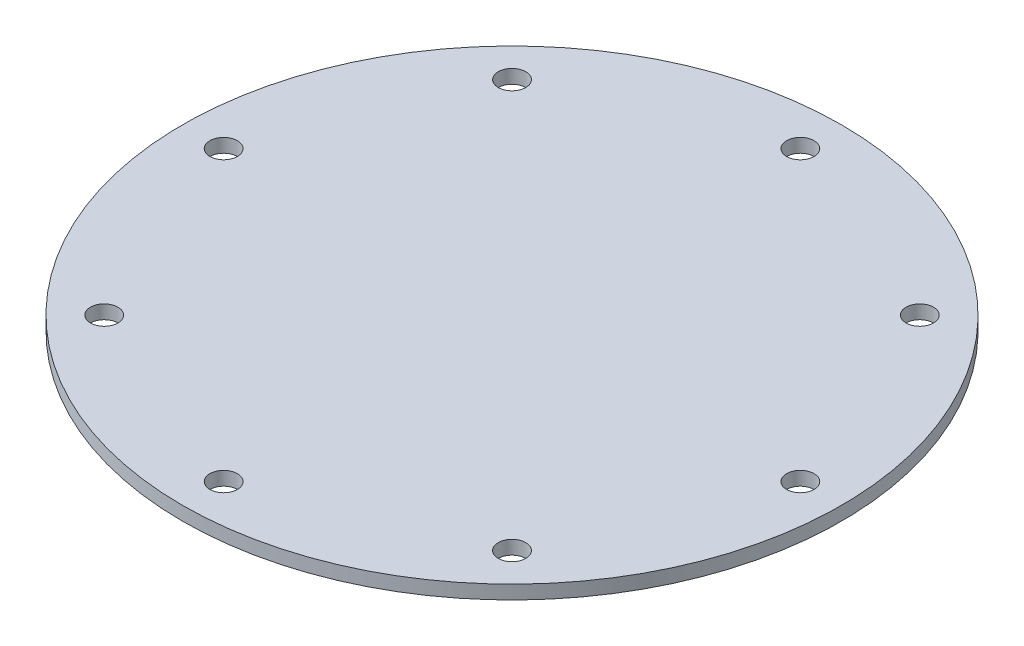
SolidWorks part; units mm, degrees
ref_plane "Спереди" through (0, 0, 0) normal (0, 0, 1) x (1, 0, 0)
ref_plane "Сверху" through (0, 0, 0) normal (0, 1, 0) x (1, 0, 0)
ref_plane "Справа" through (0, 0, 0) normal (1, 0, 0) x (0, 0, -1)
sketch "Эскиз9" plane through (0, 0, 0) normal (0, 1, 0) x (1, 0, 0)
  circle A0 centre (0, 0) radius 120
  dimension "D1" = 240
extrude "Бобышка-Вытянуть1" add sketch "Эскиз9" along normal blind 5 separate body contours A0
ref_axis "Ось1" through (0, 50, 0) along (0, -1, 0)
hole_wizard "Диаметр отверстия Ø10.0 (10)1" positions "Эскиз12" profile "Эскиз13" hole size "Ø10.0" standard "DIN"
sketch "Эскиз12" plane through (0, 5, 0) normal (0, 1, 0) x (1, 0, 0)
  line L0 (-50, 0) -> (50, 0) construction
  point P0 (105, 0)
  point P4 (0, 0)
  dimension "D1" = 105
sketch "Эскиз13" plane through (105, 5, 0) normal (1, 0, 0) x (0, 0, 1)
  line L0 (0, 0) -> (0, 18.0043)
  line L1 (0, 18.0043) -> (5, 15)
  line L2 (5, 15) -> (5, 0)
  line L5 (5, 0) -> (0, 0)
  line L10 (0, 18.0043) -> (-5, 15) construction
  line L11 (0, -6.35) -> (0, 107.95) construction
  dimension "Диаметр отверстия" = 10
  dimension "Глубина отверстия" = 15
  dimension "Угол заточки сверла" = 118
pattern_circular "Круговой массив1" count 8 over 360 about axis through (0, 50, 0) along (0, -1, 0) of "Диаметр отверстия Ø10.0 (10)1"
